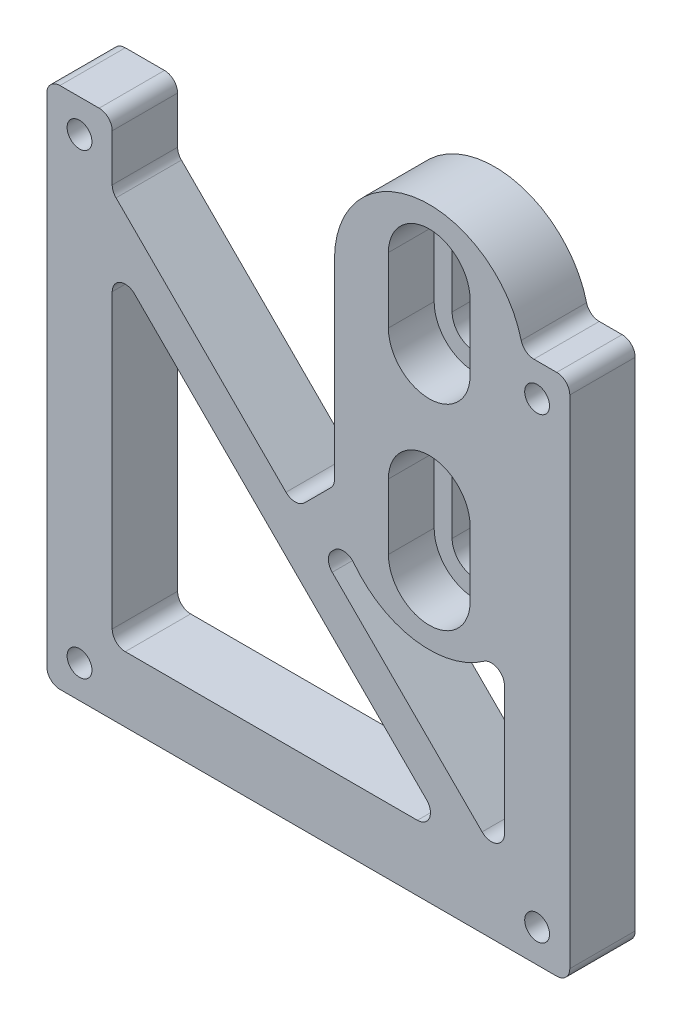
SolidWorks part; units mm, degrees
ref_plane "Front Plane" through (0, 0, 0) normal (0, 0, 1) x (1, 0, 0)
ref_plane "Top Plane" through (0, 0, 0) normal (0, 1, 0) x (1, 0, 0)
ref_plane "Right Plane" through (0, 0, 0) normal (1, 0, 0) x (0, 0, -1)
sketch "Sketch1" plane through (0, 0, 0) normal (0, 0, 1) x (1, 0, 0)
  line L5 (29.25, 39) -> (29.25, 24) construction
  line L11 (37.5, 37.5) -> (2.5, 37.5) construction
  line L12 (37.5, 37.5) -> (37.5, 2.5) construction
  line L20 (29.25, 24) -> (29.25, 39) construction
  line L25 (37.5, 2.5) -> (2.5, 2.5) construction
  line L32 (2.5, 37.5) -> (2.5, 2.5) construction
  line L38 (0, 0) -> (40, 0)
  line L40 (0, 0) -> (0, 40)
  line L43 (5, 35) -> (5, 40)
  line L44 (0, 40) -> (40, 40)
  line L45 (40, 0) -> (40, 40)
  line L46 (22, 24) -> (22, 39)
  line L47 (36.5, 24) -> (36.5, 39)
  line L48 (5, 35) -> (35, 5)
  line L49 (5, 35) -> (35, 35)
  line L50 (5, 35) -> (5, 5)
  line L51 (5, 5) -> (35, 5)
  line L52 (35, 35) -> (35, 5)
  line L53 (5, 30.7574) -> (30.7574, 5)
  line L54 (22, 24) -> (19, 21)
  line L55 (21.1213, 18.8787) -> (22.8453, 20.6026)
  circle A3 centre (37.5, 37.5) radius 0.95
  circle A5 centre (37.5, 2.5) radius 0.95
  circle A19 centre (2.5, 37.5) radius 0.95
  circle A20 centre (2.5, 2.5) radius 0.95
  circle A21 centre (29.25, 39) radius 1.75
  circle A22 centre (29.25, 24) radius 1.75
  arc A23 (22, 24) -> (36.5, 24) centre (29.25, 24) ccw
  arc A24 (36.5, 39) -> (22, 39) centre (29.25, 39) ccw
  point P18 (29.25, 31.5)
  dimension "D4" = 2.5
  dimension "D5" = 2.5
  dimension "D12" = 5
  dimension "D13" = 5
  dimension "D14" = 3
  dimension "D15" = 3
  dimension "D7" = 40
  dimension "D1" = 1.9
  dimension "D3" = 3.5
  dimension "D10" = 7.25
  dimension "D2" = 15
  dimension "D6" = 35
  dimension "D8" = 29.25
  dimension "D9" = 24
  dimension "D11" = 5
extrude "Boss-Extrude1" add sketch "Sketch1" along normal blind 5 contours A24 L47 A23 L52 L51 L50 L49 L46 L44 L40 L38 L45 A20 A19 A5 A3 | L44 A24 A21 | L47 A24 L44 A21 L46 L49 L52 A23 | L46 A23 L52 L49 A22 | L50 L53 L51 L48 | A23 L54 L48 L55 region at (0.5657, 20, 0) region at (30.8427, 35.0298, 0) region at (29.25, 42.6766, 0) region at (18.9662, 18.9662, 0) region at (21.1135, 21.1899, 0) region at (28.607, 26.5543, 0)
sketch "Sketch5" plane through (0, 0, 0) normal (0, 0, 1) x (1, 0, 0)
  line L1 (0, 40) -> (40, 40)
  line L2 (0, 40) -> (0, -6.25)
  line L3 (0, -6.25) -> (40, -6.25)
  line L4 (40, 40) -> (40, -6.25)
  line L6 (40, 0) -> (40, 40) construction
  line L7 (0, 0) -> (40, 0) construction
  dimension "D1" = 6.25
sketch "Sketch6" plane through (0, 0, 5) normal (0, 0, 1) x (1, 0, 0)
  circle A0 centre (29.25, 39) radius 3.125
  circle A1 centre (29.25, 24) radius 3.125
  dimension "D1" = 6.25
extrude "Cut-Extrude1" cut sketch "Sketch6" against normal blind 3.2
sketch "Sketch7" plane through (0, 0, 5) normal (0, 0, 1) x (1, 0, 0)
  line L0 (29.25, 26.5) -> (29.25, 21.5) construction
  line L1 (32.375, 26.5) -> (32.375, 21.5)
  line L2 (26.125, 26.5) -> (26.125, 21.5)
  line L3 (29.25, 26.5) -> (29.25, 21.5) construction
  line L4 (31, 26.5) -> (31, 21.5)
  line L5 (27.5, 26.5) -> (27.5, 21.5)
  line L6 (29.25, 41.5) -> (29.25, 36.5) construction
  line L7 (32.375, 41.5) -> (32.375, 36.5)
  line L8 (26.125, 41.5) -> (26.125, 36.5)
  line L9 (29.25, 41.5) -> (29.25, 36.5) construction
  line L10 (31, 41.5) -> (31, 36.5)
  line L11 (27.5, 41.5) -> (27.5, 36.5)
  arc A0 (32.375, 26.5) -> (26.125, 26.5) centre (29.25, 26.5) ccw
  arc A1 (26.125, 21.5) -> (32.375, 21.5) centre (29.25, 21.5) ccw
  arc A2 (31, 26.5) -> (27.5, 26.5) centre (29.25, 26.5) ccw
  arc A3 (27.5, 21.5) -> (31, 21.5) centre (29.25, 21.5) ccw
  arc A4 (32.375, 41.5) -> (26.125, 41.5) centre (29.25, 41.5) ccw
  arc A5 (26.125, 36.5) -> (32.375, 36.5) centre (29.25, 36.5) ccw
  arc A6 (31, 41.5) -> (27.5, 41.5) centre (29.25, 41.5) ccw
  arc A7 (27.5, 36.5) -> (31, 36.5) centre (29.25, 36.5) ccw
  circle A15 centre (29.25, 24) radius 1.75 construction
  circle A16 centre (29.25, 24) radius 3.125 construction
  point P2 (29.25, 24)
  point P7 (29.25, 24)
  point P14 (29.25, 39)
  point P21 (29.25, 39)
  circle M7 centre (29.25, 39) radius 3.125
  circle M8 centre (29.25, 24) radius 3.125
  dimension "D1" = 5
extrude "Cut-Extrude2" cut sketch "Sketch7" against normal through all contours L11 A7 L10 A6 M7 | L5 A3 L4 A2 M8 | A2 M8 | A3 M8 | A7 M7 | A6 L11 A7 L10 region at (29.25, 27.483, 5) region at (29.25, 24, 5) region at (29.25, 20.517, 5) region at (29.25, 39, 5) region at (29.25, 35.517, 5)
extrude "Cut-Extrude3" cut sketch "Sketch7<3>" against normal blind 3.5
sketch "Sketch7<3>" plane through (0, 0, 5) normal (0, 0, 1) x (1, 0, 0) same geometry as "Sketch7"
fillet "Fillet1" radius 1 16 edges at (5, 30.7574, 2.5) (40, 40, 2.5) (36.4307, 40, 2.5) (35, 19.5841, 2.5) (22.8453, 20.6026, 2.5) (21.1213, 18.8787, 2.5) (22, 24, 2.5) (19, 21, 2.5) (30.7574, 5, 2.5) (35, 5, 2.5) (5, 5, 2.5) (5, 35, 2.5) (5, 40, 2.5) (0, 40, 2.5) (40, 0, 2.5) (0, 0, 2.5)
